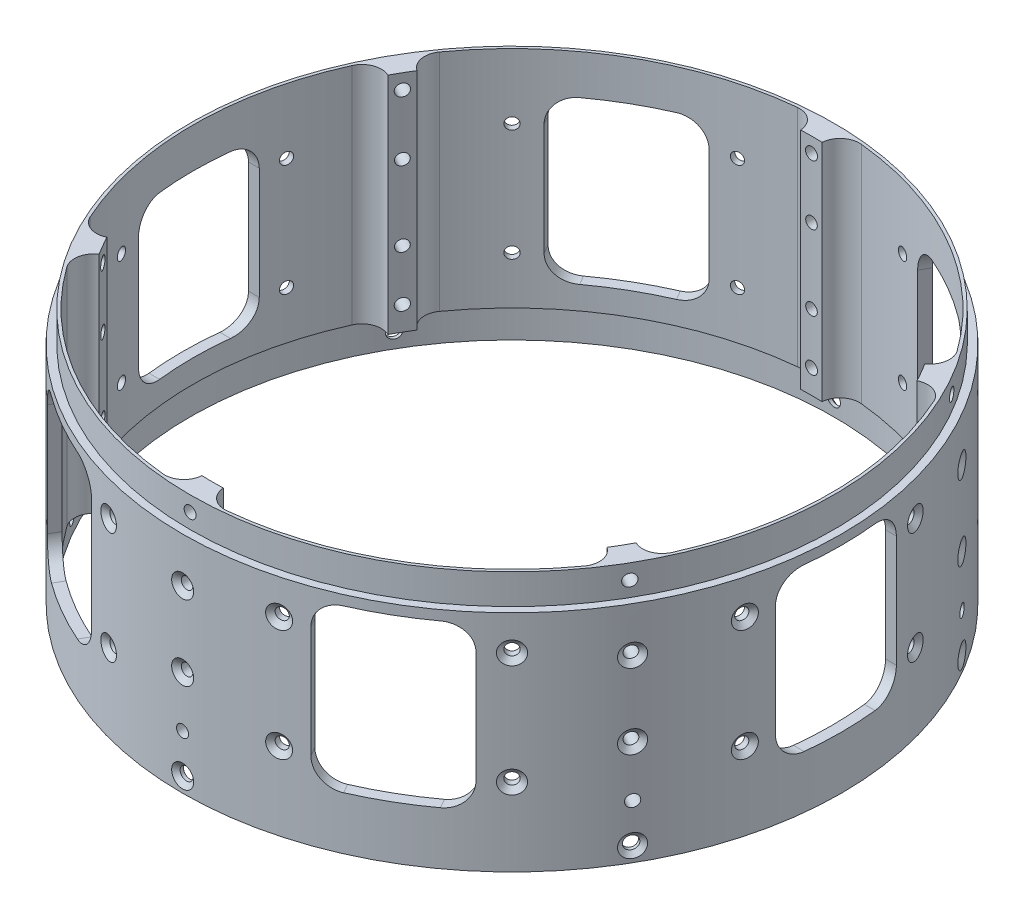
SolidWorks part; units mm, degrees
material "6061-T6 (SS)"
ref_plane "Front Plane" through (0, 0, 0) normal (0, 0, 1) x (1, 0, 0)
ref_plane "Top Plane" through (0, 0, 0) normal (0, 1, 0) x (1, 0, 0)
ref_plane "Right Plane" through (0, 0, 0) normal (1, 0, 0) x (0, 0, -1)
sketch "Sketch1" plane through (0, 0, 0) normal (0, 0, 1) x (1, 0, 0)
  line L0 (0, 42.3951) -> (0, -32.8937) construction
  line L1 (0, -32.131) -> (0, 32.131) construction
  line L2 (76.2, -57.15) -> (76.2, 0)
  line L3 (76.2, 0) -> (81.8896, 0)
  line L4 (81.8896, 0) -> (81.8896, -7.6708)
  line L5 (81.8896, -7.6708) -> (83.82, -7.6708)
  line L6 (83.82, -7.6708) -> (83.82, -64.77)
  line L7 (83.82, -64.77) -> (81.9404, -64.77)
  line L8 (81.9404, -64.77) -> (81.9404, -57.15)
  line L9 (81.9404, -57.15) -> (76.2, -57.15)
  line L10 (81.8896, -7.62) -> (84.2911, -7.62) construction
  dimension "D5" = 5.6896
  dimension "D10" = 76.2
  dimension "D2" = 7.62
  dimension "D4" = 7.62
  dimension "D6" = 7.62
revolve "Revolve1" add sketch "Sketch1" angle 360 about L0
sketch "Sketch2" plane through (0, 0, 0) normal (0, 1, 0) x (1, 0, 0)
  line L0 (0, 0) -> (0, 112.6688) construction
  line L1 (0, -32.131) -> (0, 32.131) construction
  line L2 (0, 0) -> (-128.6689, 74.287) construction
  line L3 (0, 0) -> (-50.2561, 87.0461) construction
  line L4 (0, 0) -> (-7.6343, 75.8166) construction
  arc A0 (-7.6343, 75.8166) -> (-61.8419, 44.5198) centre (0, 0) ccw construction
  arc A1 (-8.128, 80.7194) -> (-65.841, 47.3988) centre (0, 0) ccw
  arc A2 (-7.1406, 70.9138) -> (-57.8428, 41.6409) centre (0, 0) ccw
  arc A3 (-7.1406, 70.9138) -> (-8.128, 80.7194) centre (-7.6343, 75.8166) ccw
  arc A4 (-65.841, 47.3988) -> (-57.8428, 41.6409) centre (-61.8419, 44.5198) ccw
  circle A5 centre (0, 0) radius 81.8896 construction
  circle A7 centre (0, 0) radius 76.2 construction
  point P5 (-38.1, 65.9911)
  dimension "D2" = 0.762
  dimension "D1" = 60
  dimension "D3" = 30
  dimension "D4" = 5.75
extrude "Cut-Extrude1" cut sketch "Sketch2" against normal through all
pattern_circular "CirPattern1" count 6 over 360 about axis through (0, 42.3951, 0) along (0, 1, 0) of "Cut-Extrude1"
ref_plane "Plane1" through (0, 0, 83.82) normal (0, 0, 1) x (1, 0, 0)
hole_wizard "Tapped Hole for #4-40 Helicoil1" positions "Sketch3" profile "Sketch4" tap size "#4-40" standard "Helicoil® Inch"
sketch "Sketch3" plane through (0, 0, 83.82) normal (0, 0, 1) x (1, 0, 0)
  line L0 (81.8896, 0) -> (-81.8896, 0) construction
  line L1 (2.7181, 0) -> (-2.7181, 0) construction
  line L2 (2.7181, 0) -> (-2.7181, 0) construction
  line L3 (0, 0) -> (0, -3.81) construction
  line L5 (-2.7181, -57.15) -> (2.7181, -57.15) construction
  line L6 (-2.7181, -57.15) -> (2.7181, -57.15) construction
  line L7 (0, -57.15) -> (0, -51.054) construction
  point P0 (0, -3.81)
  point P20 (0, -51.054)
  point P46 (0, 0)
  point P47 (0, 0)
  dimension "D1" = 3.81
  dimension "D2" = 6.096
cosmetic thread "Hole Thread4" parameters "D1"=3.556, "D2"=3.7414
cosmetic thread "Hole Thread5" parameters "D1"=3.556, "D2"=3.7414
sketch "Sketch4" plane through (0, -3.81, 83.82) normal (1, 0, 0) x (0, -1, 0)
  line L0 (0, 0) -> (0, 26.3157)
  line L1 (0, 26.3157) -> (1.524, 25.4)
  line L2 (1.524, 25.4) -> (1.524, 0)
  line L5 (1.524, 0) -> (0, 0)
  line L10 (0, 26.3157) -> (-1.524, 25.4) construction
  line L11 (0, -6.35) -> (0, 107.95) construction
  dimension "Tap Drill Dia." = 3.048
  dimension "Tap Drill Depth" = 25.4
  dimension "Drill Angle" = 118
hole_wizard "CSK for #4 Flat Head Machine Screw (100)1" positions "Sketch5" profile "Sketch6" countersink size "#4" standard "ANSI Inch"
sketch "Sketch5" plane through (0, 0, 83.82) normal (0, 0, 1) x (1, 0, 0)
  line L0 (-2.7181, -57.15) -> (2.7181, -57.15) construction
  line L1 (-2.7181, -57.15) -> (2.7181, -57.15) construction
  line L2 (0, -57.15) -> (0, -60.96) construction
  point P0 (0, -60.96)
  dimension "D1" = 3.81
sketch "Sketch6" plane through (0, -60.96, 83.82) normal (1, 0, 0) x (0, -1, 0)
  line L0 (0, 0) -> (0, 26.3806)
  line L1 (0, 26.3806) -> (1.6319, 25.4)
  line L2 (1.6319, 25.4) -> (1.6319, 1.0284)
  line L3 (1.6319, 1.0284) -> (2.8575, 0)
  line L5 (2.8575, 0) -> (0, 0)
  line L6 (-1.6319, 1.0284) -> (-2.8575, 0) construction
  line L10 (0, 26.3806) -> (-1.632, 25.4) construction
  line L11 (0, -6.35) -> (0, 107.95) construction
  dimension "Hole Dia." = 3.2639
  dimension "Hole Depth" = 25.4
  dimension "Near C'Sink Dia." = 5.715
  dimension "Near C'Sink Angle" = 100
  dimension "Drill Angle" = 118
hole_wizard "CSK for #4 Flat Head Machine Screw (100)2" positions "Sketch8" profile "Sketch9" countersink size "#4" standard "ANSI Inch"
sketch "Sketch8" plane through (0, 0, 83.82) normal (0, 0, 1) x (1, 0, 0)
  line L0 (-2.7181, -57.15) -> (2.7181, -57.15) construction
  point P0 (0, -19.05)
  point P2 (0, -38.1)
  point P6 (0, -57.15)
  point P7 (0, 0)
  dimension "D1" = 19.05
  dimension "D2" = 38.1
sketch "Sketch9" plane through (0, -19.05, 83.82) normal (1, 0, 0) x (0, -1, 0)
  line L0 (0, 0) -> (0, 26.2852)
  line L1 (0, 26.2852) -> (1.4732, 25.4)
  line L2 (1.4732, 25.4) -> (1.4732, 1.1616)
  line L3 (1.4732, 1.1616) -> (2.8575, 0)
  line L5 (2.8575, 0) -> (0, 0)
  line L6 (-1.4732, 1.1616) -> (-2.8575, 0) construction
  line L10 (0, 26.2852) -> (-1.4732, 25.4) construction
  line L11 (0, -6.35) -> (0, 107.95) construction
  dimension "Hole Dia." = 2.9464
  dimension "Hole Depth" = 25.4
  dimension "Near C'Sink Dia." = 5.715
  dimension "Near C'Sink Angle" = 100
  dimension "Drill Angle" = 118
pattern_circular "CirPattern2" count 6 over 360 about axis through (0, 42.3951, 0) along (0, 1, 0) of "Tapped Hole for #4-40 Helicoil1", "CSK for #4 Flat Head Machine Screw (100)1", "CSK for #4 Flat Head Machine Screw (100)2"
sketch "Sketch7" plane through (0, 0, 0) normal (1, 0, 0) x (0, 0, -1)
  line L1 (-9.017, -10.16) -> (9.017, -10.16)
  line L2 (-15.367, -16.51) -> (-15.367, -44.958)
  line L3 (-9.017, -51.308) -> (9.017, -51.308)
  line L4 (15.367, -16.51) -> (15.367, -44.958)
  line L5 (-15.367, -10.16) -> (15.367, -51.308) construction
  line L6 (-15.367, -51.308) -> (15.367, -10.16) construction
  arc A0 (-15.367, -44.958) -> (-9.017, -51.308) centre (-9.017, -44.958) ccw
  arc A1 (9.017, -51.308) -> (15.367, -44.958) centre (9.017, -44.958) ccw
  arc A2 (15.367, -16.51) -> (9.017, -10.16) centre (9.017, -16.51) ccw
  arc A3 (-9.017, -10.16) -> (-15.367, -16.51) centre (-9.017, -16.51) ccw
  point P0 (0, -30.734)
  dimension "D4" = 6.35
  dimension "D1" = 41.148
  dimension "D2" = 30.734
  dimension "D3" = 10.16
extrude "Cut-Extrude2" cut sketch "Sketch7" along normal through all
sketch "Sketch10" plane through (0, -7.6708, 0) normal (0, 1, 0) x (1, 0, 0)
  line L0 (83.82, 0) -> (73.3608, 0)
  line L1 (83.82, 8.7224) -> (83.82, -9.9429) construction
  line L2 (72.989, 19.5573) -> (80.9639, 21.6942)
  line L3 (79.0853, 28.7051) -> (82.8425, 14.6833) construction
  arc A0 (83.3336, -9.017) -> (83.3336, 9.017) centre (0, 0) ccw construction
  circle A1 centre (0, 0) radius 83.82 construction
  dimension "D1" = 15
ref_plane "Plane2" through (80.9639, -7.6708, -21.6942) normal (0.9659, 0, -0.2588) x (-0.2588, 0, -0.9659)
hole_wizard "CSK for #4 Flat Head Machine Screw (100)3" positions "Sketch11" profile "Sketch12" countersink size "#4" standard "ANSI Inch"
sketch "Sketch11" plane through (80.9639, -7.6708, -21.6942) normal (0.9659, 0, -0.2588) x (-0.2588, 0, -0.9659)
  line L0 (0, -37.2872) -> (0, -8.8392) construction
  line L1 (0, -8.8392) -> (0, 0) construction
  line L3 (0, -23.0632) -> (-6.4831, -23.0632) construction
  line L5 (0, -8.8392) -> (-6.4831, -8.8392) construction
  line L7 (-6.4831, -37.2872) -> (-6.4831, -8.8392) construction
  point P0 (0, -8.8392)
  point P2 (0, -37.2872)
  point P18 (0, 0)
  point P20 (0, 0)
sketch "Sketch12" plane through (80.9639, -16.51, -21.6942) normal (0, 1, 0) x (-0.2588, 0, -0.9659)
  line L0 (0, 0) -> (0, 26.2852)
  line L1 (0, 26.2852) -> (1.4732, 25.4)
  line L2 (1.4732, 25.4) -> (1.4732, 1.1616)
  line L3 (1.4732, 1.1616) -> (2.8575, 0)
  line L5 (2.8575, 0) -> (0, 0)
  line L6 (-1.4732, 1.1616) -> (-2.8575, 0) construction
  line L10 (0, 26.2852) -> (-1.4732, 25.4) construction
  line L11 (0, -6.35) -> (0, 107.95) construction
  dimension "Hole Dia." = 2.9464
  dimension "Hole Depth" = 25.4
  dimension "Near C'Sink Dia." = 5.715
  dimension "Near C'Sink Angle" = 100
  dimension "Drill Angle" = 118
mirror "Mirror1" about plane through (0, 0, 0) normal (0, 0, 1) of "CSK for #4 Flat Head Machine Screw (100)3"
pattern_circular "CirPattern5" count 6 over 360 about axis through (0, -7.6708, 0) along (0, 1, 0) of "Cut-Extrude2", "Mirror1"
equation "\"nominalLength\"=2.25"
equation "\"D8@Sketch1\"=\"nominalLength\""
